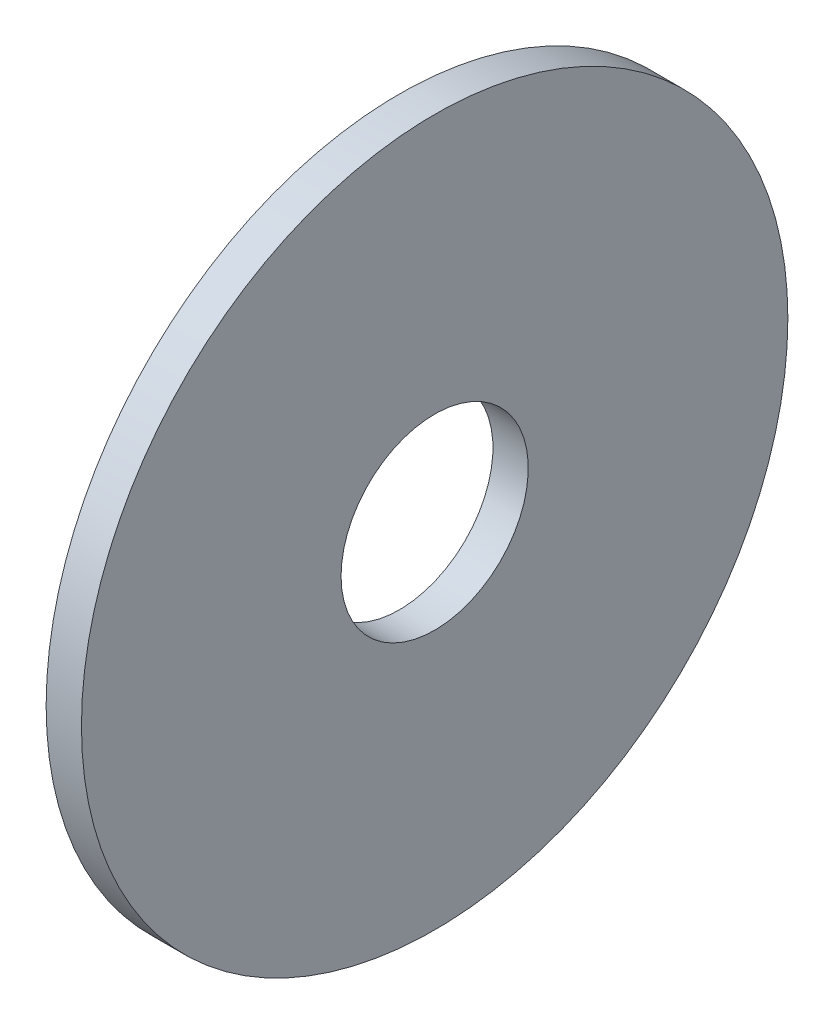
SolidWorks part; units mm, degrees
ref_plane "Plan1" through (0, 0, 0) normal (0, 0, 1) x (1, 0, 0)
ref_plane "Plan2" through (0, 0, 0) normal (0, 1, 0) x (1, 0, 0)
ref_plane "Plan3" through (0, 0, 0) normal (1, 0, 0) x (0, 0, -1)
sketch "Esquisse1" plane through (0, 0, 0) normal (0, 1, 0) x (1, 0, 0)
  line L0 (0, 0) -> (40, 0) construction
  line L2 (0, 10) -> (1, 10)
  line L3 (0, 10) -> (0, 2.65)
  line L4 (0, 2.65) -> (1, 2.65)
  line L5 (1, 10) -> (1, 2.65)
  dimension "D1" = 2.65
  dimension "D2" = 10
  dimension "D3" = 1
revolve "Base-Révolution" add sketch "Esquisse1" angle 360 about L0
ref_axis "Axe1" through (-50, 0, 0) along (1, 0, 0)
